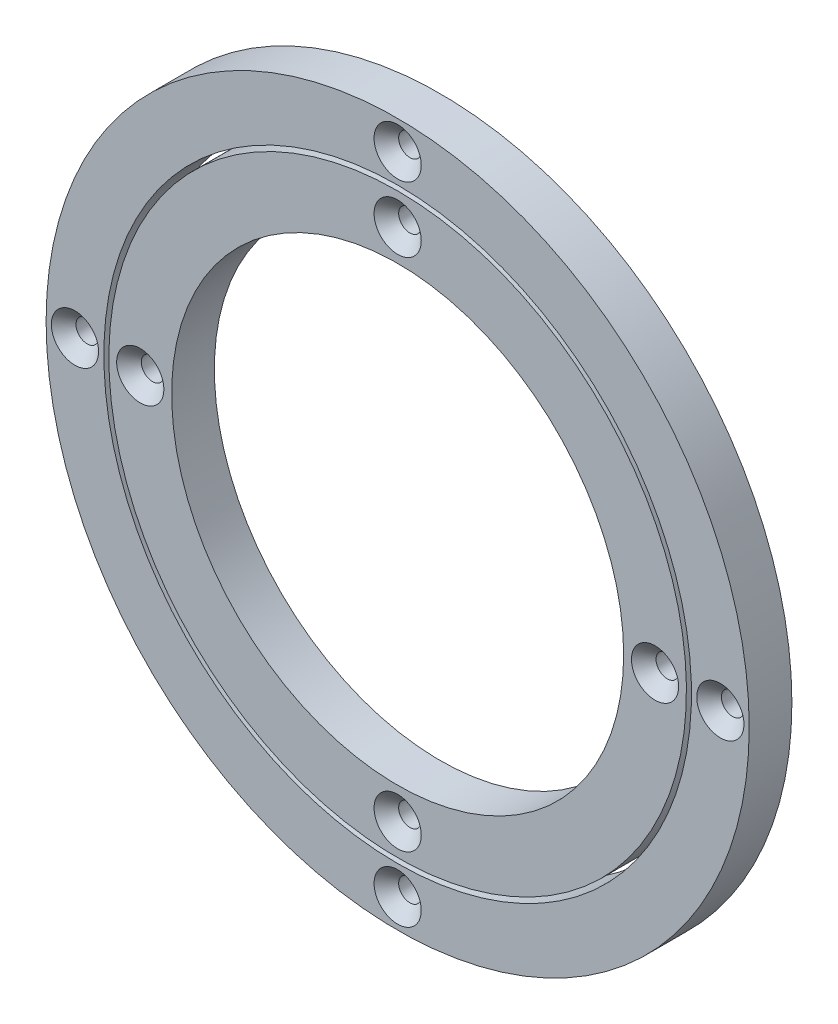
SolidWorks part; units mm, degrees
ref_plane "Front Plane" through (0, 0, 0) normal (1, 0, 0) x (0, 1, 0)
ref_plane "Top Plane" through (0, 0, 0) normal (0, 0, 1) x (0, 1, 0)
ref_plane "Right Plane" through (0, 0, 0) normal (0, 1, 0) x (-1, 0, 0)
sketch "Sketch2" plane through (0, 0, 0) normal (0, 0, 1) x (0, 1, 0)
  circle A0 centre (0, 0) radius 70
  circle A1 centre (0, 0) radius 45
  circle A2 centre (0, 0) radius 58
  point P6 (0, 0)
  point P7 (0, 0)
  point P8 (0, 0)
  point P9 (0, 0)
  point P10 (0, 0)
  dimension "D1" = 140
  dimension "D2" = 90
  dimension "D3" = 13
extrude "Boss-Extrude1" add sketch "Sketch2" along normal blind 8.5 contours A0 | A1
extrude "Cut-Extrude-Thin2" cut sketch "Sketch2<3>" along normal through all thin contours A2 thin type mid plane wall 1
sketch "Sketch2<3>" plane through (0, 0, 0) normal (0, 0, 1) x (0, 1, 0) same geometry as "Sketch2"
hole_wizard "CSK for M4 Countersunk Flat Head Screw1" positions "Sketch3" profile "Sketch4" countersink size "M4" standard "ISO" end condition through all
sketch "Sketch3" plane through (0, 0, 8.5) normal (0, 0, 1) x (1, 0, 0)
  line L0 (58.5, 0) -> (70, 0) construction
  line L1 (-70, 0) -> (-58.5, 0) construction
  line L3 (45, 0) -> (57.5, 0) construction
  circle A0 centre (0, 0) radius 70 construction
  circle A1 centre (0, 0) radius 58.5 construction
  circle A2 centre (0, 0) radius 45 construction
  circle A3 centre (0, 0) radius 57.5 construction
  point P0 (64.25, 0)
  point P40 (64.25, 0)
  point P51 (0, -64.25)
  point P52 (-64.25, 0)
  point P53 (0, 64.25)
  point P106 (-64.25, 0)
  point P117 (51.25, 0)
  point P127 (0, -51.25)
  point P128 (-51.25, 0)
  point P129 (0, 51.25)
  point P135 (0, -51.25)
  point P136 (-51.25, 0)
  point P137 (0, 51.25)
  dimension "D1" = 4
  dimension "D2" = 4
  dimension "D3" = 4
sketch "Sketch4" plane through (64.25, 0, 8.5) normal (1, 0, 0) x (0, -1, 0)
  line L0 (0, 0) -> (0, 8.5)
  line L1 (0, 8.5) -> (2.25, 8.5)
  line L2 (2.25, 8.5) -> (2.25, 2.45)
  line L3 (2.25, 2.45) -> (4.7, 0)
  line L5 (4.7, 0) -> (0, 0)
  line L6 (-2.25, 2.45) -> (-4.7, 0) construction
  line L11 (0, -6.35) -> (0, 107.95) construction
  dimension "Thru Hole Dia." = 4.5
  dimension "Thru Hole Depth" = 8.5
  dimension "Near C'Sink Dia." = 9.4
  dimension "Near C'Sink Angle" = 90
